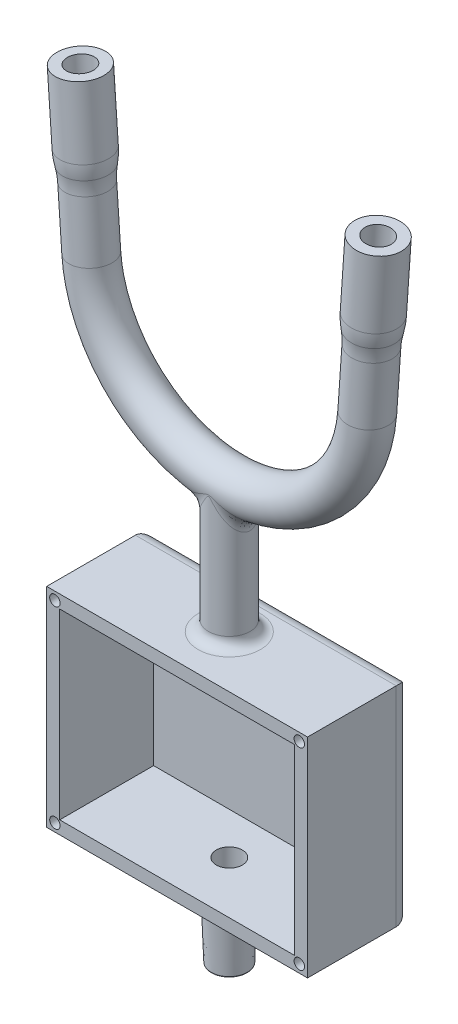
SolidWorks part; units mm, degrees
ref_plane "Alzado" through (0, 0, 0) normal (0, 0, 1) x (1, 0, 0)
ref_plane "Planta" through (0, 0, 0) normal (0, 1, 0) x (1, 0, 0)
ref_plane "Vista lateral" through (0, 0, 0) normal (1, 0, 0) x (0, 0, -1)
sketch "Croquis1" plane through (0, 0, 0) normal (0, 0, 1) x (1, 0, 0)
  line L0 (0, 0) -> (0, 191.7552) construction
  line L1 (5, 160.1093) -> (40.914, 157.6226) construction
  line L2 (40.914, 157.6226) -> (30, 0) construction
  line L3 (27.506, 0.1727) -> (38.5804, 160.1115) construction
  line L4 (27.506, 0.1727) -> (30, 0) construction
  line L5 (5, 160.1093) -> (4.8273, 157.6153) construction
  line L6 (4.8273, 157.6153) -> (-19.3231, 159.2875) construction
  line L7 (24.0182, -50.199) -> (31.2919, 54.8506) construction
  circle A0 centre (27.506, 0.1727) radius 2.5 construction
  spline S0 degree 3 poles (4.8273, 157.6153) (36.4183, 155.4279) (39.0186, 166.4413) (27.506, 0.1727) knots 0 0 0 0 1 1 1 1
  dimension "D5" = 5
  dimension "D6" = 95
  dimension "D7" = 500
  dimension "D1" = 30
  dimension "D2" = 10
  dimension "D3" = 36
  dimension "D4" = 158
ref_plane "Plano1" through (27.506, 0.1727, 0) normal (-0.0691, -0.9976, 0) x (-0.9976, 0.0691, 0)
sketch "Croquis6" plane through (0, 0, 0) normal (0, 1, 0) x (1, 0, 0)
  line L1 (-37.5, 2.5) -> (37.5, 2.5)
  line L2 (-37.5, 2.5) -> (-37.5, -2.5)
  line L3 (-37.5, -2.5) -> (37.5, -2.5)
  line L4 (37.5, 2.5) -> (37.5, -2.5)
  line L5 (-37.5, 2.5) -> (37.5, -2.5) construction
  line L6 (-37.5, -2.5) -> (37.5, 2.5) construction
  point P0 (0, 0)
  dimension "D1" = 5
  dimension "D2" = 75
sketch "Croquis11" plane through (0, 0, 0) normal (0, 0, 1) x (1, 0, 0)
  line L0 (27.506, 0.1727) -> (28.536, 15.1373)
  line L1 (0, 0) -> (0, -39.8273) construction
  line L2 (27.506, 0.1727) -> (26.4525, -15.133)
  arc A0 (0, -39.8273) -> (26.4525, -15.133) centre (0, -13.3123) ccw
  spline S0 degree 3 poles (4.8273, 157.6153) (36.4183, 155.4279) (39.0186, 166.4413) (27.506, 0.1727) knots 0 0 0 0 1 1 1 1 construction
  dimension "D1" = 15
  dimension "D2" = 40
ref_plane "Plano2" through (28.536, 15.1373, 0) normal (0.0687, 0.9976, 0) x (0.9976, -0.0687, 0)
sketch "Croquis12" plane through (28.536, 15.1373, 0) normal (0.0687, 0.9976, 0) x (0.9976, -0.0687, 0)
  circle A0 centre (0, 0) radius 4
  dimension "D1" = 8
sweep "Barrer1" add profiles "Croquis12" path "Croquis11"
sketch "Croquis13" plane through (1.1716, 17.0208, 0) normal (0.0687, 0.9976, 0) x (0.9976, -0.0687, 0)
  circle A2 centre (27.4292, 0) radius 4.5
  circle A3 centre (27.4292, 0) radius 4.5
  dimension "D1" = 0.5
extrude "Saliente-Extruir1" add sketch "Croquis13" against normal blind 15
fillet "Redondeo3" radius 15 1 edges at (23.5154, 0.4474, 0)
fillet "Redondeo4" radius 15 1 edges at (23.0166, 0.4817, 0)
mirror "Simetría7" about plane through (0, 0, 0) normal (1, 0, 0) of bodies 138
sketch "Croquis14" plane through (0, 0, 0) normal (0, 0, 1) x (1, 0, 0)
  line L0 (0, -39.8273) -> (0, -64.8273)
  line L1 (0, -35.8273) -> (0, -43.8273) construction
  dimension "D1" = 25
ref_plane "Plano3" through (0, -64.8273, 0) normal (0, -1, 0) x (-1, 0, 0)
sketch "Croquis15" plane through (0, -64.8273, 0) normal (0, -1, 0) x (-1, 0, 0)
  circle A0 centre (0, 0) radius 3.975
  dimension "D1" = 7.95
extrude "Saliente-Extruir2" add sketch "Croquis15" against normal up to vertex (25 mm away) up to point (0, -39.8273, 0)
fillet "Redondeo5" radius 3 1 edges at (-0.0002, -40.2738, -3.975)
sketch "Sketch1" plane through (1.1716, 17.0208, 0) normal (0.0687, 0.9976, 0) x (0.9976, -0.0687, 0)
  circle A0 centre (27.4292, 0) radius 2.5
  dimension "D1" = 5
sketch "Sketch2" plane through (0, 0, 0) normal (0, 0, 1) x (1, 0, 0)
  line L0 (28.536, 15.1373) -> (27.506, 0.1727)
  line L1 (27.506, 0.1727) -> (26.4525, -15.133)
  line L2 (0, 0) -> (0, -39.8273) construction
  line L3 (-27.506, 0.1727) -> (-26.4525, -15.133)
  line L4 (-28.536, 15.1373) -> (-27.506, 0.1727)
  arc A0 (26.4525, -15.133) -> (-26.4525, -15.133) centre (0, -13.3123) cw
sweep "Cut-Sweep2" cut profiles "Sketch1" path "Sketch2"
sketch "Sketch3" plane through (0, -64.8273, 0) normal (0, -1, 0) x (1, 0, 0)
  circle A0 centre (0, 0) radius 2.5
  dimension "D1" = 5
sketch "Sketch4" plane through (0, -64.8273, 0) normal (0, -1, 0) x (-1, 0, 0)
  line L1 (-25, -10) -> (25, -10)
  line L2 (-25, -10) -> (-25, 10)
  line L3 (-25, 10) -> (25, 10)
  line L4 (25, -10) -> (25, 10)
  line L5 (-25, -10) -> (25, 10) construction
  line L6 (-25, 10) -> (25, -10) construction
  point P0 (0, 0)
  dimension "D1" = 50
  dimension "D2" = 20
extrude "Boss-Extrude1" add sketch "Sketch4" along normal blind 40
sketch "Sketch5" plane through (0, -104.8273, 0) normal (0, -1, 0) x (1, 0, 0)
  circle A0 centre (0, 0) radius 3.975
  dimension "D1" = 7.95
extrude "Boss-Extrude2" add sketch "Sketch5" along normal blind 15 draft 2
sketch "Sketch6" plane through (0, -119.8273, 0) normal (0, -1, 0) x (1, 0, 0)
  circle A0 centre (0, 0) radius 2.5
  dimension "D1" = 5
extrude "Cut-Extrude2" cut sketch "Sketch6" against normal blind 25
sketch "Sketch7" plane through (0, 0, 10) normal (0, 0, 1) x (1, 0, 0)
  line L0 (-25, -84.8273) -> (54.233, -84.8273) construction
  line L1 (-25, -104.8273) -> (-25, -64.8273) construction
  line L2 (0, -84.8273) -> (0, -17.7212) construction
  line L4 (-22.5, -67.3273) -> (22.5, -67.3273)
  line L5 (-22.5, -67.3273) -> (-22.5, -102.3273)
  line L6 (-22.5, -102.3273) -> (22.5, -102.3273)
  line L7 (22.5, -67.3273) -> (22.5, -102.3273)
  line L8 (-22.5, -67.3273) -> (22.5, -102.3273) construction
  line L9 (-22.5, -102.3273) -> (22.5, -67.3273) construction
  dimension "D1" = 45
  dimension "D2" = 35
extrude "Cut-Extrude3" cut sketch "Sketch7" against normal blind 18
extrude "Cut-Extrude4" cut sketch "Sketch3" against normal blind 25 and the other way blind 5
hole_wizard "Ø2.0mm Dowel Hole1" positions "Sketch10" profile "Sketch12" hole size "Ø2.0" standard "ANSI Metric"
sketch "Sketch10" plane through (0, 0, 10) normal (0, 0, 1) x (1, 0, 0)
  point P0 (-23.4222, -66.3566)
  point P2 (23.4226, -66.3566)
  point P4 (23.4226, -103.2623)
  point P6 (-23.4222, -103.2623)
sketch "Sketch12" plane through (-23.4222, -66.3566, 10) normal (1, 0, 0) x (0, -1, 0)
  line L0 (0, 0) -> (0, 6.6009)
  line L1 (0, 6.6009) -> (1, 6)
  line L2 (1, 6) -> (1, 0)
  line L5 (1, 0) -> (0, 0)
  line L10 (0, 6.6009) -> (-1, 6) construction
  line L11 (0, -6.35) -> (0, 107.95) construction
  dimension "Hole Dia." = 2
  dimension "Hole Depth" = 6
  dimension "Drill Angle" = 118
fillet "Fillet1" radius 3 4 edges at (-25, -84.8273, -10) (0, -104.8273, -10) (25, -84.8273, -10) (0, -64.8273, -10)
fillet "Fillet2" radius 2 2 edges at (3.975, -64.8273, 0) (0, -104.8273, -3.975)
fillet "Fillet3" radius 0.2 1 edges at (0, -119.8273, -3.4512)
